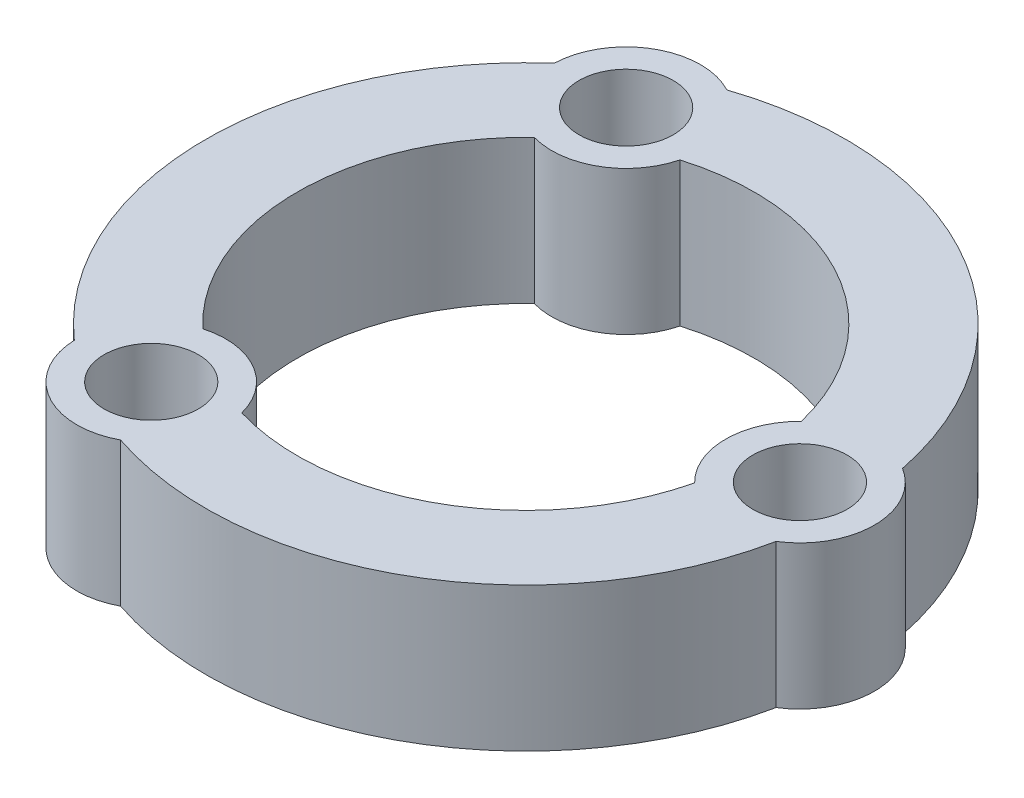
SolidWorks part; units mm, degrees
material "ABS"
ref_plane "Front Plane" through (0, 0, 0) normal (0, 0, 1) x (1, 0, 0)
ref_plane "Top Plane" through (0, 0, 0) normal (0, 1, 0) x (1, 0, 0)
ref_plane "Right Plane" through (0, 0, 0) normal (1, 0, 0) x (0, 0, -1)
sketch "Sketch1" plane through (0, 0, 0) normal (0, 1, 0) x (1, 0, 0)
  arc A0 (21.7892, 4.3921) -> (-7.0909, 21.0661) centre (0, 0) ccw
  arc A1 (15.4392, 3.7047) -> (15.4392, -3.7047) centre (19.0525, 0) ccw
  circle A2 centre (-9.5263, -16.4999) radius 3.175 construction
  circle A3 centre (-9.5262, 16.4999) radius 3.175 construction
  circle A4 centre (19.0525, 0) radius 3.175 construction
  circle A5 centre (-9.5262, 16.4999) radius 3.175
  circle A6 centre (19.0525, 0) radius 3.175
  circle A7 centre (-9.5263, -16.4999) radius 3.175
  arc A8 (-4.5112, -15.2231) -> (-10.928, -11.5184) centre (-9.5263, -16.4999) ccw
  arc A9 (21.7892, -4.3921) -> (21.7892, 4.3921) centre (19.0525, 0) ccw
  arc A10 (-7.0909, 21.0661) -> (-14.6983, 16.674) centre (-9.5262, 16.4999) ccw
  arc A11 (15.4392, 3.7047) -> (-4.5112, 15.2231) centre (0, 0) ccw
  circle A12 centre (19.0525, 0) radius 5.175 construction
  arc A13 (-10.928, 11.5184) -> (-4.5112, 15.2231) centre (-9.5262, 16.4999) ccw
  circle A14 centre (-9.5262, 16.4999) radius 5.175 construction
  arc A15 (-10.928, 11.5184) -> (-10.928, -11.5184) centre (0, 0) ccw
  arc A16 (-14.6983, 16.674) -> (-14.6983, -16.674) centre (0, 0) ccw
  arc A17 (-4.5112, -15.2231) -> (15.4392, -3.7047) centre (0, 0) ccw
  arc A18 (-7.0909, -21.0661) -> (21.7892, -4.3921) centre (0, 0) ccw
  circle A19 centre (-9.5263, -16.4999) radius 5.175 construction
  arc A20 (-14.6983, -16.674) -> (-7.0909, -21.0661) centre (-9.5263, -16.4999) ccw
  point P1 (30.1365, 0)
  point P20 (-4.9245, 20.2425)
  point P29 (-4.9245, -20.2425)
  dimension "D1" = 2
extrude "Boss-Extrude1" add sketch "Sketch1" along normal blind 10 contours A7 | A5 | A6 | A16 A20 A18 A9 A0 A10 A5 A6 A7 A17 A8 A15 A13 A11 A1 region at (23.5845, 0, 0) region at (-9.5262, 0, -16.4999) region at (19.0525, 0, 0) region at (-9.5262, 0, 16.4999)
sketch "Sketch3" plane through (0, 10, 0) normal (0, 1, 0) x (1, 0, 0)
  circle A1 centre (19.0525, 0) radius 3.275
  arc A3 (15.4392, 3.7047) -> (15.4392, -3.7047) centre (19.0525, 0) ccw construction
  dimension "D1" = 6.55
extrude "Cut-Extrude1" cut sketch "Sketch3" against normal blind 7.5
pattern_circular "CirPattern1" count 3 every 120 about axis through (0, 10, 0) along (0, 1, 0) of "Cut-Extrude1"
